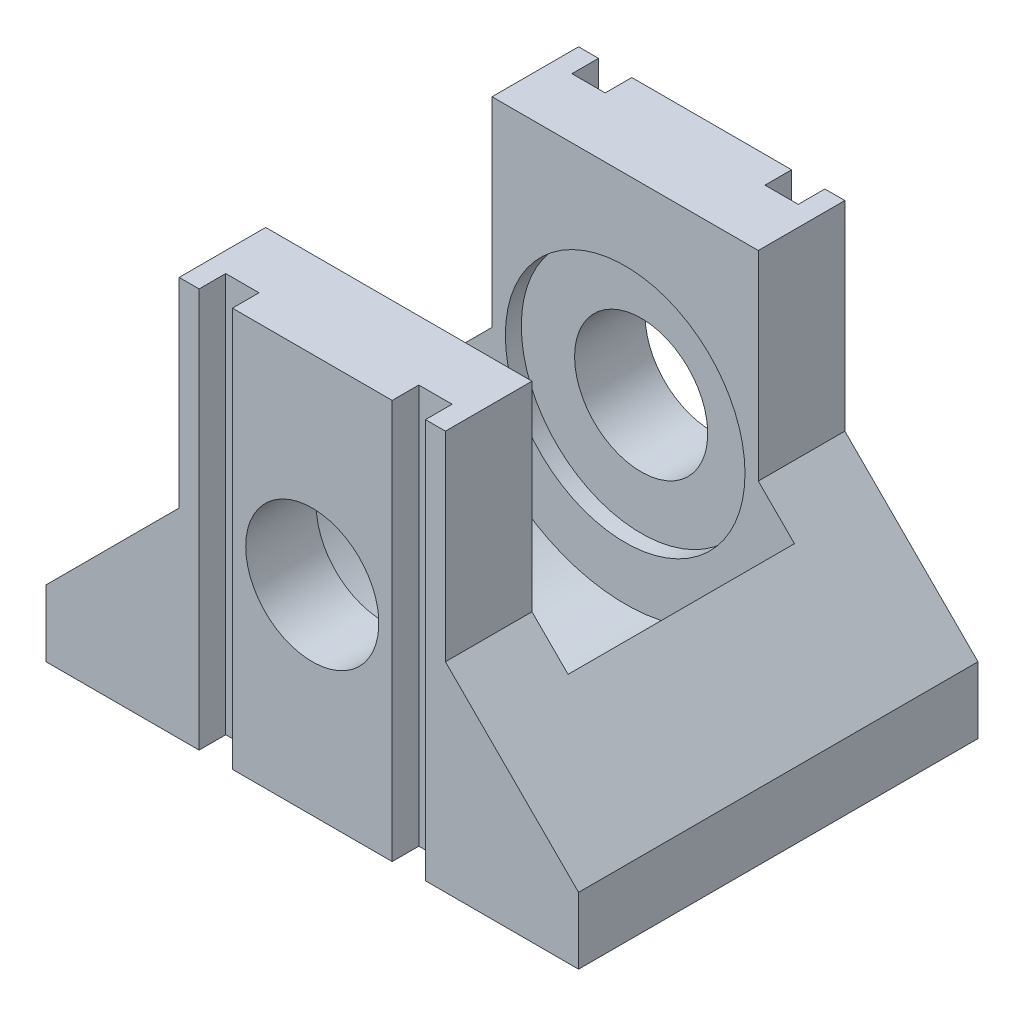
SolidWorks part; units mm, degrees
ref_plane "Płaszczyzna przednia" through (0, 0, 0) normal (0, 0, 1) x (1, 0, 0)
ref_plane "Płaszczyzna górna" through (0, 0, 0) normal (0, 1, 0) x (1, 0, 0)
ref_plane "Płaszczyzna prawa" through (0, 0, 0) normal (1, 0, 0) x (0, 0, -1)
sketch "Sketch5" plane through (0, 0, 0) normal (0, 0, 1) x (1, 0, 0)
  line L1 (-40, 15) -> (0, 15)
  line L2 (-40, 15) -> (-40, 0)
  line L3 (-40, 0) -> (0, 0)
  line L4 (0, 15) -> (0, 0)
  dimension "D1" = 40
  dimension "D2" = 15
extrude "Boss-Extrude2" add sketch "Sketch5" along normal blind 15
sketch "Sketch6" plane through (0, 0, 0) normal (0, 0, -1) x (-1, 0, 0)
  line L0 (0, 15) -> (40, 15) construction
  circle A0 centre (20, 15) radius 13
  dimension "D1" = 26
extrude "Cut-Extrude4" cut sketch "Sketch6" against normal blind 8.5
sketch "Sketch7" plane through (0, 0, 15) normal (0, 0, 1) x (1, 0, 0)
  line L0 (0, 15) -> (-40, 15) construction
  circle A0 centre (-20, 15) radius 2.5
  dimension "D1" = 5
extrude "Cut-Extrude5" cut sketch "Sketch7" against normal blind 4.5 contours A0
mirror "Mirror5" about plane through (0, 0, 0) normal (0, 0, 1) of "Cut-Extrude4", "Cut-Extrude5", "Boss-Extrude2"
sketch "Sketch8" plane through (0, 0, 0) normal (0, -1, 0) x (1, 0, 0)
  line L0 (-40, 0) -> (0, 0) construction
  line L1 (-20, 15) -> (-20, -15) construction
  line L2 (-40, 15) -> (-40, -15) construction
  line L3 (0, 15) -> (0, -15) construction
  line L4 (-40, -15) -> (0, -15) construction
  line L5 (-40, 15) -> (0, 15) construction
  circle A0 centre (-33, 9.5) radius 4.8
  circle A1 centre (-7, 9.5) radius 4.8
  circle A2 centre (-7, -9.5) radius 4.8
  circle A3 centre (-33, -9.5) radius 4.8
  dimension "D1" = 9.6
  dimension "D2" = 5.5
  dimension "D3" = 7
chamfer "Chamfer8" distance 10 angle 45 2 edges at (-40, 15, 0) (0, 15, 0)
sketch "Sketch10" plane through (0, 0, -8.5) normal (0, 0, 1) x (1, 0, 0)
  line L0 (-30, 15) -> (-22.5, 15)
  line L1 (-17.5, 15) -> (-10, 15)
  line L2 (-30, 30) -> (-10, 30)
  line L3 (-30, 30) -> (-30, 15)
  line L4 (-30, 15) -> (-22.5, 15)
  line L5 (-10, 30) -> (-10, 15)
  line L6 (-17.5, 15) -> (-10, 15)
  circle A0 centre (-20, 15) radius 2.5
  arc A1 (-30, 15) -> (-10, 15) centre (-20, 15) ccw
  arc A2 (-22.5, 15) -> (-17.5, 15) centre (-20, 15) ccw construction
  circle A3 centre (-20, 15) radius 10 construction
  line M3 (-10, 15) -> (-30, 15)
  line M7 (-10, 15) -> (-30, 15)
  dimension "D1" = 15
extrude "Boss-Extrude3" add sketch "Sketch10" against normal blind 6.5 contours A0 L5 L2 L3 M7 M3 | A0 region at (-20, 22.7178, -8.5)
ref_plane "Plane1" through (0, 0, 0) normal (0, 0, -1) x (-1, 0, 0)
mirror "Mirror6" about plane through (0, 0, 0) normal (0, 0, -1) of "Boss-Extrude3"
extrude "Cut-Extrude8" cut sketch "Sketch8" against normal blind 3
sketch "Sketch9" plane through (0, 0, 0) normal (0, -1, 0) x (1, 0, 0)
  line L0 (-20, 15) -> (-20, -15) construction
  line L1 (-40, 0) -> (0, 0) construction
  line L3 (-40, 15) -> (0, 15) construction
  line L4 (-40, 15) -> (-40, -15) construction
  line L5 (-40, -15) -> (0, -15) construction
  line L6 (0, 15) -> (0, -15) construction
  line L7 (-11.5, 13) -> (-14, 13)
  line L8 (-28.5, 15) -> (-26, 15)
  line L9 (-28.5, 15) -> (-28.5, 13)
  line L10 (-28.5, 13) -> (-26, 13)
  line L11 (-26, 15) -> (-26, 13)
  line L12 (-14, 15) -> (-14, 13)
  line L13 (-11.5, 15) -> (-14, 15)
  line L14 (-11.5, 15) -> (-11.5, 13)
  line L15 (-11.5, -15) -> (-11.5, -13)
  line L16 (-11.5, -15) -> (-14, -15)
  line L17 (-14, -15) -> (-14, -13)
  line L18 (-11.5, -13) -> (-14, -13)
  line L19 (-28.5, -13) -> (-26, -13)
  line L20 (-26, -15) -> (-26, -13)
  line L21 (-28.5, -15) -> (-26, -15)
  line L22 (-28.5, -15) -> (-28.5, -13)
  dimension "D1" = 2.5
  dimension "D2" = 2
  dimension "D3" = 6
extrude "Cut-Extrude7" cut sketch "Sketch9" against normal blind 52
sketch "Sketch11" plane through (0, 0, 8.5) normal (0, 0, -1) x (-1, 0, 0)
  circle A0 centre (20, 15) radius 5
  arc A1 (7.2864, 12.2864) -> (32.7136, 12.2864) centre (20, 15) ccw construction
  dimension "D1" = 10
extrude "Cut-Extrude9" cut sketch "Sketch11" against normal mid plane 90
sketch "Sketch12" plane through (0, 0, 8.5) normal (0, 0, -1) x (-1, 0, 0)
  circle A0 centre (20, 15) radius 5
  circle A1 centre (20, 15) radius 5 construction
  circle A2 centre (20, 15) radius 9
  dimension "D1" = 18
extrude "Cut-Extrude11" cut sketch "Sketch12" against normal blind 1.2
mirror "Mirror7" about plane through (0, 0, 0) normal (0, 0, -1) of "Cut-Extrude11"
